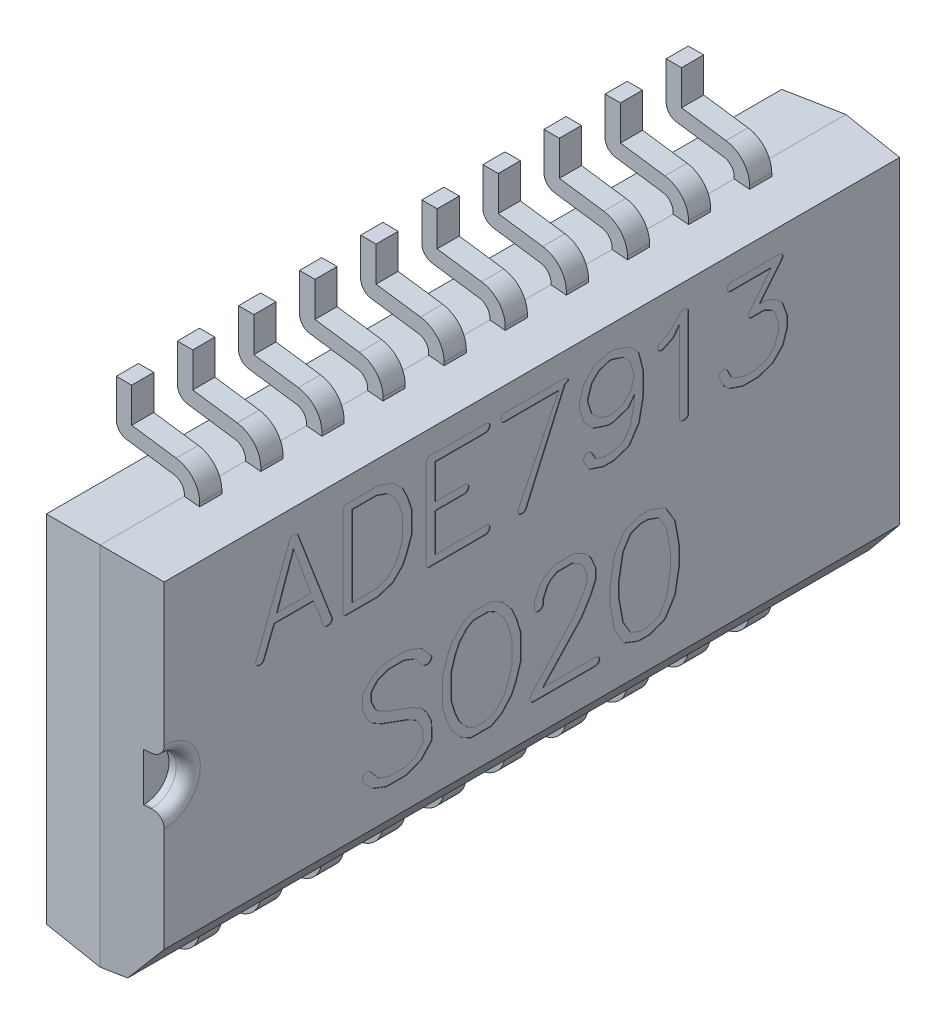
SolidWorks part; units mm, degrees
ref_plane "Front Plane" through (0, 0, 0) normal (0, 0, 1) x (1, 0, 0)
ref_plane "Top Plane" through (0, 0, 0) normal (0, 1, 0) x (1, 0, 0)
ref_plane "Right Plane" through (0, 0, 0) normal (1, 0, 0) x (0, 0, -1)
sketch "Sketch1" plane through (0, 0, 0) normal (1, 0, 0) x (0, 0, -1)
  line L1 (-7.75, 3.8) -> (7.75, 3.8)
  line L2 (-7.75, 3.8) -> (-7.75, -3.8)
  line L3 (-7.75, -3.8) -> (7.75, -3.8)
  line L4 (7.75, 3.8) -> (7.75, -3.8)
  line L5 (-7.75, 3.8) -> (7.75, -3.8) construction
  line L6 (-7.75, -3.8) -> (7.75, 3.8) construction
  point P0 (0, 0)
  dimension "D1" = 7.6
  dimension "D2" = 15.5
extrude "Boss-Extrude1" add sketch "Sketch1" along normal mid plane 2.45 draft 5
chamfer "Chamfer1" distance 0.7 angle 45 1 edges at (1.225, -3.6928, 0)
sketch "Sketch3" plane through (1.225, 0, 0) normal (1, 0, 0) x (0, 0, -1)
  line L0 (-7.6428, 3.6928) -> (-7.6428, -2.9228) construction
  line L1 (-7.6428, 0.5) -> (-7.8928, 0.5)
  line L2 (-7.8928, 0.5) -> (-7.8928, -0.5)
  line L3 (-7.8928, -0.5) -> (-7.6428, -0.5)
  arc A0 (-7.6428, 0.5) -> (-7.6428, -0.5) centre (-7.6428, 0) cw
  dimension "D1" = 0.5
  dimension "D2" = 0.25
extrude "Cut-Extrude1" cut sketch "Sketch3" against normal blind 0.4
fillet "Fillet1" radius 0.25 1 edges at (1.225, 0, 7.1428)
sketch "Sketch5" plane through (0, 0, 0) normal (0, 0, 1) x (1, 0, 0)
  line L0 (0, 3.4486) -> (0, 3.8388)
  line L1 (0, 3.8) -> (0, -3.8) construction
  line L2 (-0.2152, 4.0864) -> (-1.1998, 4.2248)
  line L3 (-1.415, 4.4723) -> (-1.415, 5.255)
  line L4 (1.225, 3.6928) -> (1.225, 0.75) construction
  line L5 (0, 0) -> (3.3608, 0) construction
  arc A0 (-1.415, 4.4723) -> (-1.1998, 4.2248) centre (-1.165, 4.4723) ccw
  arc A1 (-0.2152, 4.0864) -> (0, 3.8388) centre (-0.25, 3.8388) cw
  point P14 (-1.415, 4.255)
  dimension "D5" = 0.25
  dimension "D1" = 2.64
  dimension "D2" = 10.51
  dimension "D3" = 1
  dimension "D4" = 98
extrude "Extrude-Thin1" add sketch "Sketch5" against normal blind 0.46 from offset 6 separate body thin
pattern_linear "LPattern1" count 10 spacing 1.27 along (0, 0, -1) of bodies 103
mirror "Mirror1" about plane through (0, 0, 0) normal (0, 1, 0) of bodies 103 104 105 106 107 108 109 110 111 112
sketch "Sketch8" plane through (1.225, 0, 0) normal (1, 0, 0) x (0, 0, -1)
  line L0 (-7.2771, 1.25) -> (7.2771, 1.25) construction
  line L1 (-7.2771, -2.25) -> (7.2771, -2.25) construction
  text T0 "ADE7913" font "SWSimp" height 2
  text T1 "SO20\r\n\r\n" font "SWSimp" height 2.25
  point P3 (0, 1.25)
  point P5 (0, 0)
  point P8 (0, -2.25)
  point P9 (0, 0)
  dimension "D1" = 1.25
  dimension "D2" = 2.25
extrude "Cut-Extrude2" cut sketch "Sketch8" against normal blind 0.01
